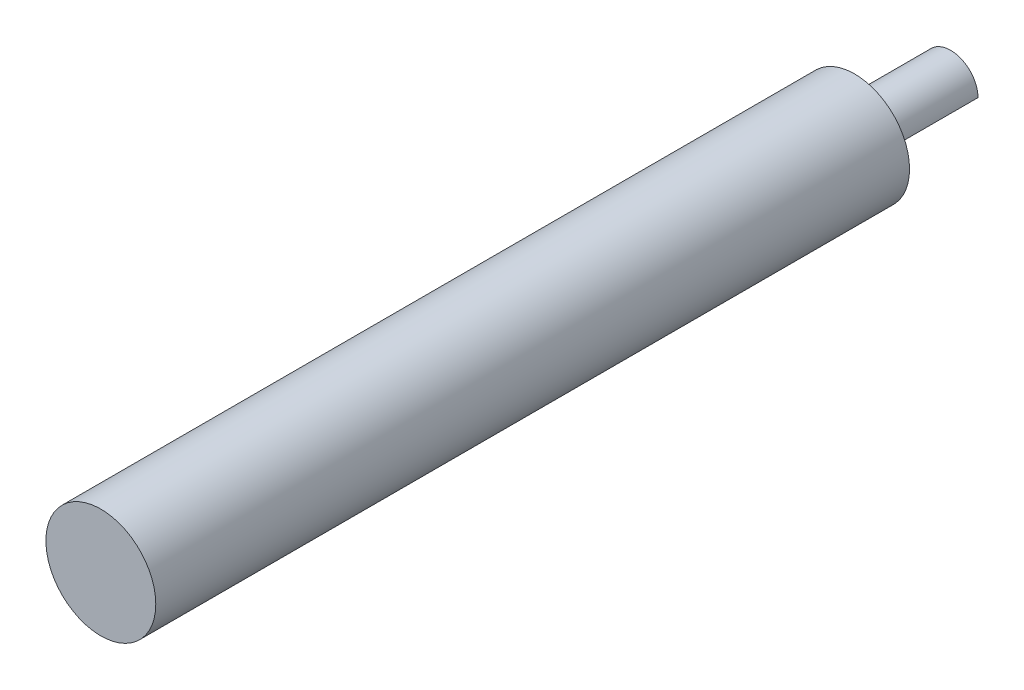
SolidWorks part; units mm, degrees
material "AISI 1020"
ref_plane "Front Plane" through (0, 0, 0) normal (0, 0, 1) x (1, 0, 0)
ref_plane "Top Plane" through (0, 0, 0) normal (0, 1, 0) x (1, 0, 0)
ref_plane "Right Plane" through (0, 0, 0) normal (1, 0, 0) x (0, 0, -1)
sketch "Sketch1" plane through (0, 0, 0) normal (0, 0, 1) x (1, 0, 0)
  circle A0 centre (0, 0) radius 3.1623
  dimension "D1" = 6.3246
extrude "Boss-Extrude1" add sketch "Sketch1" along normal blind 11.0998
sketch "Sketch2" plane through (0, 0, 0) normal (0, 0, -1) x (-1, 0, 0)
  line L0 (0.0012, -3.1623) -> (-3.1623, 0.0012)
  circle A0 centre (0, 0) radius 3.1623 construction
  dimension "D1" = 2.2352
extrude "Cut-Extrude1" cut sketch "Sketch2" against normal through all and the other way through all
sketch "Sketch3" plane through (0, 0, 11.0998) normal (0, 0, 1) x (1, 0, 0)
  circle A0 centre (0, 0) radius 6.35
  dimension "D1" = 12.7
extrude "Boss-Extrude2" add sketch "Sketch3" along normal blind 87.122
sketch "Sketch5" plane through (0, 0, 98.2218) normal (0, 0, 1) x (1, 0, 0)
  circle A0 centre (0, 0) radius 6.35
fillet "Fillet1" [suppressed] radius 1.27 type face fillet
